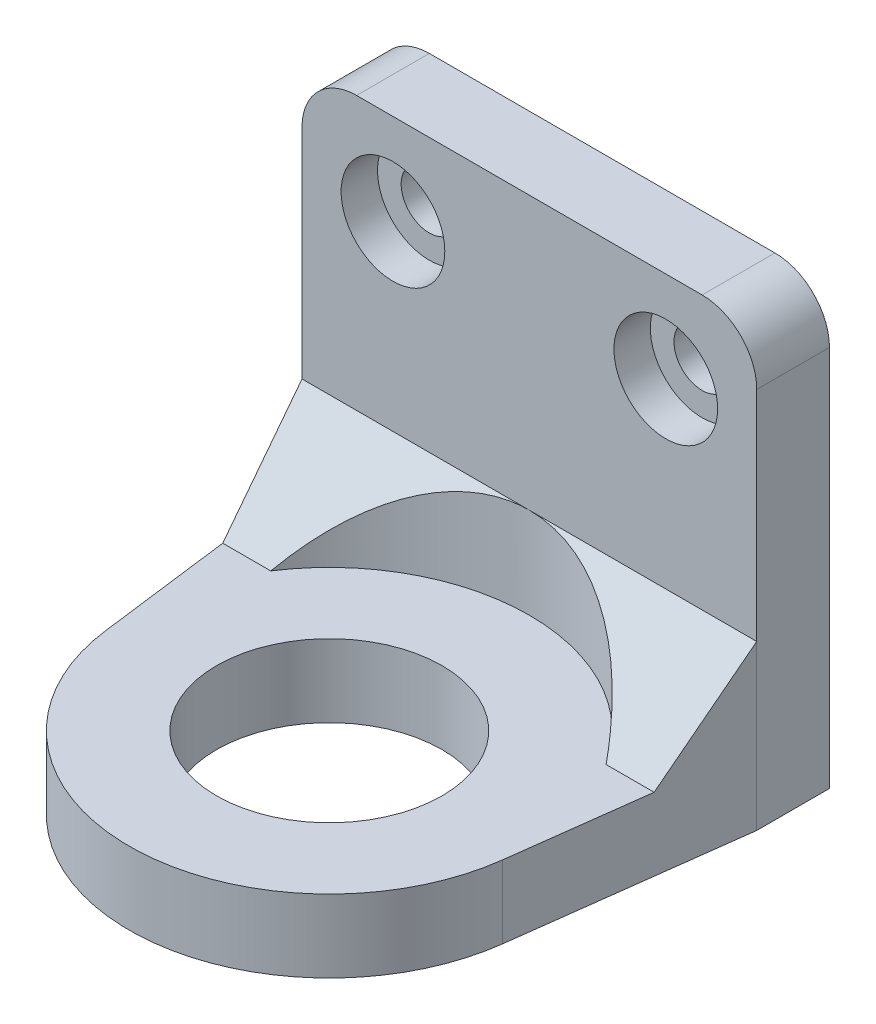
SolidWorks part; units mm, degrees
ref_plane "Front Plane" through (0, 0, 0) normal (0, 0, 1) x (1, 0, 0)
ref_plane "Top Plane" through (0, 0, 0) normal (0, 1, 0) x (1, 0, 0)
ref_plane "Right Plane" through (0, 0, 0) normal (1, 0, 0) x (0, 0, -1)
sketch "Sketch1" plane through (0, 0, 0) normal (0, 0, 1) x (1, 0, 0)
  line L5 (25, -35.5) -> (25, -19.5)
  line L6 (25, -19.5) -> (4, -19.5)
  line L7 (4, -19.5) -> (0, -19.5)
  line L8 (0, -19.5) -> (0, -35.5)
  line L9 (0, -35.5) -> (25, -35.5)
  line L10 (25, -35.5) -> (25, -25.5)
  line L12 (4, -19.5) -> (0, -19.5)
  line L13 (0, -25.5) -> (0, -35.5)
  line L14 (0, -35.5) -> (25, -35.5)
  line L25 (5, -30.5) -> (20, -30.5) construction
  line L26 (0, -25.5) -> (25, -25.5)
  circle A0 centre (5, -30.5) radius 1.55 construction
  circle A1 centre (20, -30.5) radius 1.55 construction
  circle A2 centre (5, -30.5) radius 1.55
  circle A3 centre (20, -30.5) radius 1.55
  dimension "D1" = 0
extrude "Boss-Extrude1" add sketch "Sketch1" along normal blind 4 contours L26 L13 L14 L10 A2 A3 region at (12.5, -30.5, 0)
sketch "Sketch2" plane through (0, -35.5, 0) normal (0, -1, 0) x (1, 0, 0)
  line L4 (0, 0) -> (25, 0)
  line L5 (25, 0) -> (25, 4)
  line L6 (0, 0) -> (25, 0)
  line L7 (0, 4) -> (0, 0)
  line L8 (25, 4) -> (0, 4)
  line L9 (25, 0) -> (25, 4)
  line L10 (25, 4) -> (0, 4)
  line L11 (0, 4) -> (0, 0)
  dimension "D1" = 0
extrude "Boss-Extrude2" add sketch "Sketch2" along normal blind 10
sketch "Sketch3" plane through (0, -45.5, 0) normal (0, -1, 0) x (1, 0, 0)
  line L0 (12.5, 0) -> (12.5, 36.2925) construction
  line L1 (0, 0) -> (25, 0) construction
  line L2 (25, 4) -> (0, 4) construction
  line L3 (0, 4) -> (1.5893, 16.3986)
  line L4 (25, 4) -> (23.4107, 16.3986)
  line L5 (25, 4) -> (25, 0)
  line L6 (25, 0) -> (0, 0)
  line L7 (0, 0) -> (0, 4)
  circle A1 centre (12.5, 15) radius 6 construction
  circle A2 centre (12.5, 15) radius 6.2
  arc A3 (23.4107, 16.3986) -> (1.5893, 16.3986) centre (12.5, 15) ccw
  dimension "D2" = 22
  dimension "D3" = 12
  dimension "D1" = 0.2
extrude "Boss-Extrude3" add sketch "Sketch3" along normal blind 4
chamfer "Chamfer1" distance 5 angle 45 1 edges at (12.5, -45.5, 4)
sketch "Sketch4" plane through (0, -45.5, 0) normal (0, 1, 0) x (1, 0, 0)
  circle A0 centre (12.5, -15) radius 11
extrude "Cut-Extrude1" cut sketch "Sketch4" along normal blind 10
fillet "Fillet1" radius 3 2 edges at (0, -25.5, 2) (25, -25.5, 2)
sketch "Sketch5" plane through (0, 0, 4) normal (0, 0, 1) x (1, 0, 0)
  circle A0 centre (20, -30.5) radius 2.85
  circle A1 centre (5, -30.5) radius 2.85
  dimension "D1" = 5.7
extrude "Cut-Extrude2" cut sketch "Sketch5" against normal offset from surface (2 mm away) 2 up to face at (21.55, -30.5, 0)
